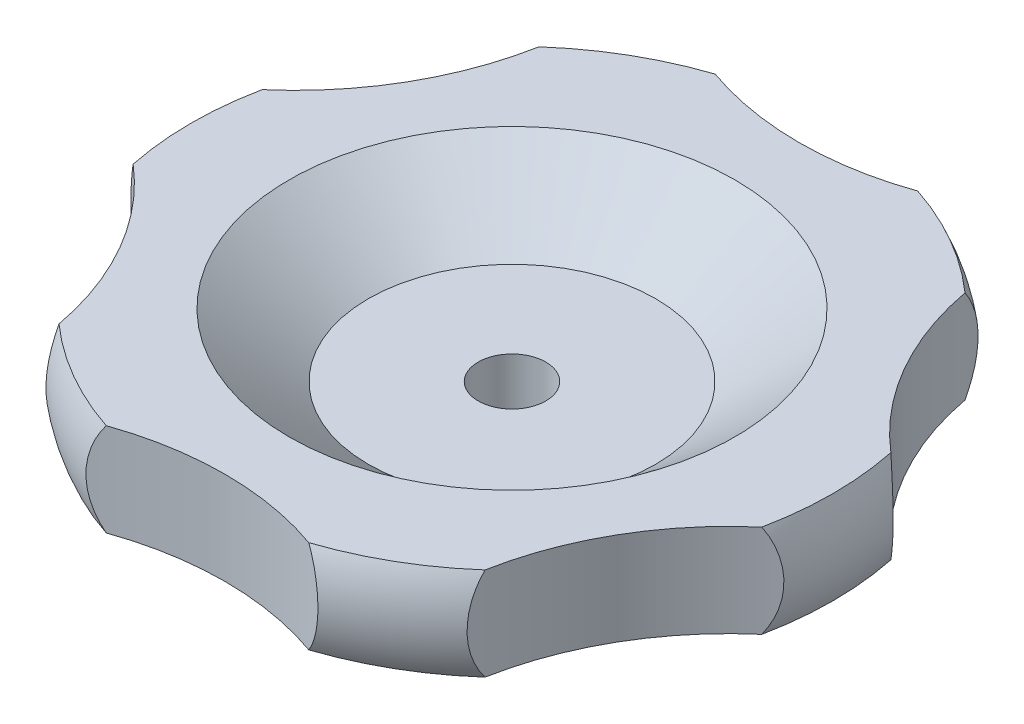
SolidWorks part; units mm, degrees
ref_plane "Plan de face" through (0, 0, 0) normal (0, 0, 1) x (1, 0, 0)
ref_plane "Plan de dessus" through (0, 0, 0) normal (0, 1, 0) x (1, 0, 0)
ref_plane "Plan de droite" through (0, 0, 0) normal (1, 0, 0) x (0, 0, -1)
sketch "Esquisse1" plane through (0, 0, 0) normal (0, 0, 1) x (1, 0, 0)
  line L0 (0, 0) -> (0, 55.7962) construction
  line L1 (-4, 12) -> (-4, 0)
  line L2 (-4, 0) -> (-13, 0)
  line L3 (-13, 0) -> (-13, 1.5)
  line L4 (-13, 1.5) -> (-18, 1.5)
  line L5 (-25, 8.5) -> (-38, 8.5)
  line L7 (-38, 19.5) -> (-26.3831, 19.5)
  line L8 (-26.3831, 19.5) -> (-17, 12)
  line L9 (-17, 12) -> (-4, 12)
  arc A0 (-18, 1.5) -> (-25, 8.5) centre (-25, 1.5) ccw
  arc A1 (-38, 19.5) -> (-38, 8.5) centre (-26.0759, 14) ccw
  dimension "D5" = 7
  dimension "D1" = 4
  dimension "D2" = 38
  dimension "D3" = 13
  dimension "D4" = 18
  dimension "D6" = 11
  dimension "D7" = 13
  dimension "D8" = 12
  dimension "D9" = 1.5
revolve "Révolution1" add sketch "Esquisse1" angle 360 about L0
sketch "Esquisse2" plane through (0, 19.5, 0) normal (0, 1, 0) x (1, 0, 0)
  line L0 (0, 0) -> (0, -70) construction
  line L1 (-18.717, -39.2482) -> (0, -70)
  line L2 (0, -70) -> (18.717, -39.2482)
  arc A0 (-18.717, -39.2482) -> (18.717, -39.2482) centre (0, -70) cw
  point P4 (0, -39.2482)
  dimension "D1" = 36
  dimension "D2" = 70
extrude "Enlèv. mat.-Extru.1" cut sketch "Esquisse2" against normal through all
ref_axis "Axe1" through (0, 0, 0) along (0, 1, 0)
pattern_circular "Répétition circulaire1" count 6 over 360 about axis through (0, 0, 0) along (0, 1, 0) of "Enlèv. mat.-Extru.1"
sketch "Esquisse3" plane through (0, 12, 0) normal (0, 1, 0) x (1, 0, 0)
  line L0 (0, 0) -> (0, 43.0014) construction
  circle A0 centre (0, 9) radius 2
  dimension "D1" = 4
  dimension "D2" = 9
extrude "Enlèv. mat.-Extru.2" [suppressed] cut sketch "Esquisse3" against normal blind 20
